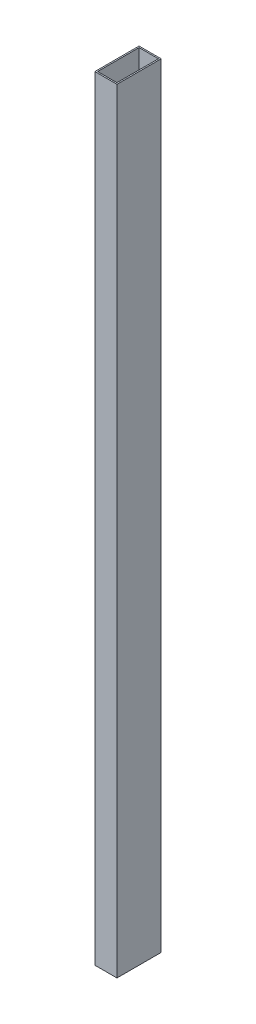
SolidWorks part; units mm, degrees
material "6061-T6 (SS)"
ref_plane "Front" through (0, 0, 0) normal (0, 0, 1) x (1, 0, 0)
ref_plane "Top" through (0, 0, 0) normal (0, 1, 0) x (1, 0, 0)
ref_plane "Right" through (0, 0, 0) normal (1, 0, 0) x (0, 0, -1)
sketch "Sketch1" plane through (0, 0, 0) normal (0, 1, 0) x (1, 0, 0)
  line L1 (12.7, 25.4) -> (-12.7, 25.4)
  line L2 (12.7, 25.4) -> (12.7, -25.4)
  line L3 (12.7, -25.4) -> (-12.7, -25.4)
  line L4 (-12.7, 25.4) -> (-12.7, -25.4)
  line L5 (12.7, 25.4) -> (-12.7, -25.4) construction
  line L6 (12.7, -25.4) -> (-12.7, 25.4) construction
  point P0 (0, 0)
  dimension "D1" = 25.4
  dimension "D2" = 50.8
extrude "Extrude-Thin1" add sketch "Sketch1" along normal blind 889 thin thin type one direction reverse wall 1.5875
